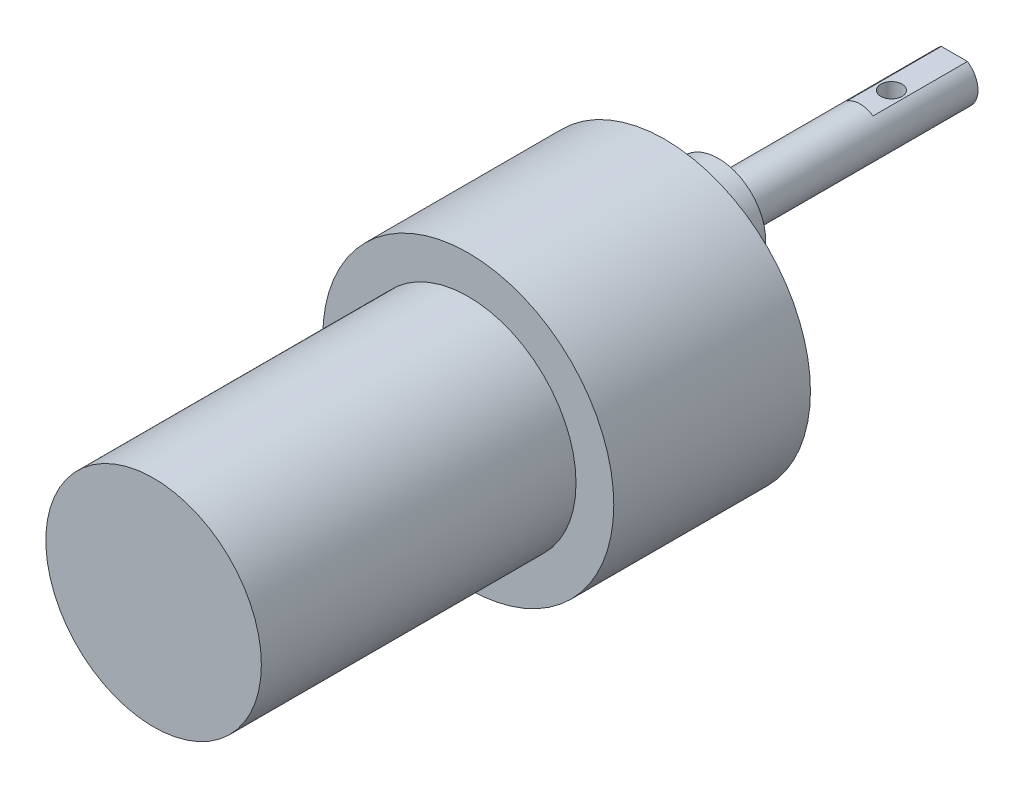
SolidWorks part; units mm, degrees
material "Plain Carbon Steel"
ref_plane "Front Plane" through (0, 0, 0) normal (0, 0, 1) x (1, 0, 0)
ref_plane "Top Plane" through (0, 0, 0) normal (0, 1, 0) x (1, 0, 0)
ref_plane "Right Plane" through (0, 0, 0) normal (1, 0, 0) x (0, 0, -1)
sketch "Sketch1" plane through (0, 0, 0) normal (0, 0, 1) x (1, 0, 0)
  circle A0 centre (0, 0) radius 18.5
  dimension "D1" = 37
extrude "Boss-Extrude1" add sketch "Sketch1" along normal blind 25
sketch "Sketch2" plane through (0, 0, 0) normal (0, 0, -1) x (-1, 0, 0)
  circle A0 centre (0, 7) radius 6
  dimension "D1" = 12
  dimension "D2" = 7
extrude "Boss-Extrude2" add sketch "Sketch2" along normal blind 6.8
sketch "Sketch3" plane through (0, 0, -6.8) normal (0, 0, -1) x (-1, 0, 0)
  circle A0 centre (0, 7) radius 3
extrude "Boss-Extrude3" add sketch "Sketch3" along normal blind 30
sketch "Sketch4" plane through (0, 0, -36.8) normal (0, 0, -1) x (-1, 0, 0)
  line L0 (-1.6583, 9.5) -> (1.6583, 9.5)
  circle A0 centre (0, 7) radius 3
  circle M2 centre (0, 7) radius 3
  dimension "D1" = 2.5
  dimension "D2" = 6
extrude "Cut-Extrude1" cut sketch "Sketch4" against normal blind 12 contours L0 M2 region at (0, 9.7015, -36.8)
sketch "Sketch5" plane through (0, 0, 25) normal (0, 0, 1) x (1, 0, 0)
  circle A0 centre (0, 0) radius 13.7
  dimension "D1" = 27.4
extrude "Boss-Extrude4" add sketch "Sketch5" along normal blind 40
sketch "Sketch6" plane through (0, 0, 0) normal (0, 0, -1) x (-1, 0, 0)
  line L0 (0, 7) -> (0, 0) construction
  line L1 (0, 0) -> (-15.75, 0) construction
  circle A0 centre (0, 0) radius 15.75 construction
  circle A1 centre (-15.75, 0) radius 1.5
  circle A2 centre (-7.875, 13.6399) radius 1.5
  circle A3 centre (7.875, 13.6399) radius 1.5
  circle A4 centre (15.75, 0) radius 1.5
  circle A5 centre (7.875, -13.6399) radius 1.5
  circle A6 centre (-7.875, -13.6399) radius 1.5
  point P19 (0, 0)
  dimension "D1" = 31.5
  dimension "D2" = 3
  dimension "D3" = 6
extrude "Cut-Extrude2" cut sketch "Sketch6" against normal blind 3.2
thread "Thread1" pitch 1.0583 method extrude profile "Thread Profile1" start angle 0, offset 0, length 3.2, pitch 1.0583, diameter 3
ref_plane "Plane1" through (17.25, 0, 0) normal (0, -1, 0) x (1, 0, 0)
sketch "Thread Profile1" plane through (17.25, 0, 0) normal (0, -1, 0) x (1, 0, 0)
  line L0 (0, 0) -> (0, 1.0583) construction
  line L11 (0, 0) -> (0, 0.926)
  line L12 (0, 0.926) -> (-0.5728, 0.5953)
  line L13 (-0.5728, 0.5953) -> (-0.5728, 0.3307)
  line L15 (-0.5728, 0.3307) -> (0, 0)
  line L17 (-0.5728, 0.463) -> (0, 0.463) construction
  point P2 (0, 0)
  dimension "Pitch" = 1.0583
  dimension "Profile_Angle" = 60
  dimension "Profile_Land" = 0.2646
  dimension "Profile_Height" = 0.5728
sketch "Sketch7" plane through (0, 9.5, 0) normal (0, 1, 0) x (1, 0, 0)
  line L0 (1.6583, 36.8) -> (-1.6583, 36.8) construction
  circle A0 centre (0, 28.8) radius 1.3505
  dimension "D1" = 8
extrude "Cut-Extrude3" cut sketch "Sketch7" against normal blind 10
sketch "Sketch8" plane through (0, 0, 0) normal (0, 0, -1) x (-1, 0, 0)
  point P0 (0, 0)
